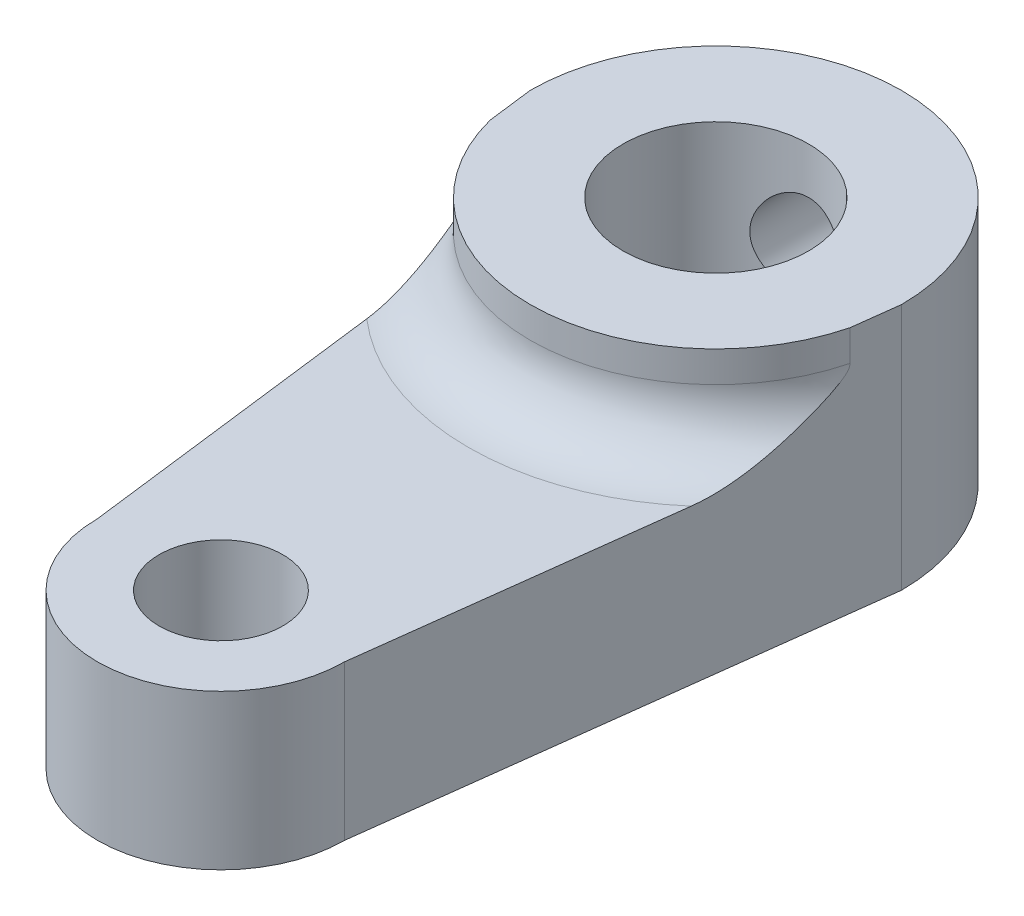
SolidWorks part; units mm, degrees
note: The reader was unsure of these and kept them because the rebuilt part matched: shared geometry of "Sketch1<3>".
ref_plane "Front Plane" through (0, 0, 0) normal (0, 0, 1) x (1, 0, 0)
ref_plane "Top Plane" through (0, 0, 0) normal (0, 1, 0) x (1, 0, 0)
ref_plane "Right Plane" through (0, 0, 0) normal (1, 0, 0) x (0, 0, -1)
sketch "Sketch1" plane through (0, 0, 0) normal (0, 1, 0) x (1, 0, 0)
  line L0 (-6, 0) -> (-4, -16)
  line L1 (6, 0) -> (4, -16)
  circle A0 centre (0, 0) radius 6
  circle A1 centre (0, 0) radius 3
  arc A2 (-4, -16) -> (4, -16) centre (0, -16) ccw
  circle A3 centre (0, -16) radius 2
  point P10 (0, 0)
  point P11 (0, 0)
  dimension "D1" = 12
  dimension "D2" = 6
  dimension "D3" = 4
  dimension "D4" = 4
  dimension "D5" = 16
extrude "Boss-Extrude1" add sketch "Sketch1" along normal blind 8 contours L1 A0 L0 A1
extrude "Boss-Extrude2" add sketch "Sketch1<3>" along normal blind 5 contours L0 A2 L1 A0 A3
sketch "Sketch1<3>" plane through (0, 0, 0) normal (0, 1, 0) x (1, 0, 0) same geometry as "Sketch1"
fillet "Fillet1" radius 2 1 edges at (0, 5, 6)
sketch "Sketch6" plane through (0, 0, 0) normal (0, -1, 0) x (1, 0, 0)
  line L0 (-4.3262, -8) -> (5.2083, -8)
  dimension "D1" = 8
surface "Surface-Extrude1" sketch "Sketch6" parameters "D1"=8
sketch "Sketch10" plane through (0, 0, -8) normal (0, 0, 1) x (1, 0, 0)
  point P0 (0, 5)
  point P4 (0, 0)
  dimension "D1" = 5
hole_wizard "M3 Tapped Hole1" positions "Sketch10" profile "Sketch9" tap size "M3" standard "ISO"
sketch "Sketch9" plane through (0, 5, -8) normal (1, 0, 0) x (0, 1, 0)
  line L0 (0, 0) -> (0, 9.4013)
  line L1 (0, 9.4013) -> (1.5, 8.5)
  line L2 (1.5, 8.5) -> (1.5, 0)
  line L5 (1.5, 0) -> (0, 0)
  line L10 (0, 9.4013) -> (-1.5, 8.5) construction
  line L11 (0, -6.35) -> (0, 107.95) construction
  dimension "Tap Drill Dia." = 3
  dimension "Tap Drill Depth" = 8.5
  dimension "Drill Angle" = 118
cosmetic thread "Hole Thread1" parameters "D1"=6, "D2"=3
